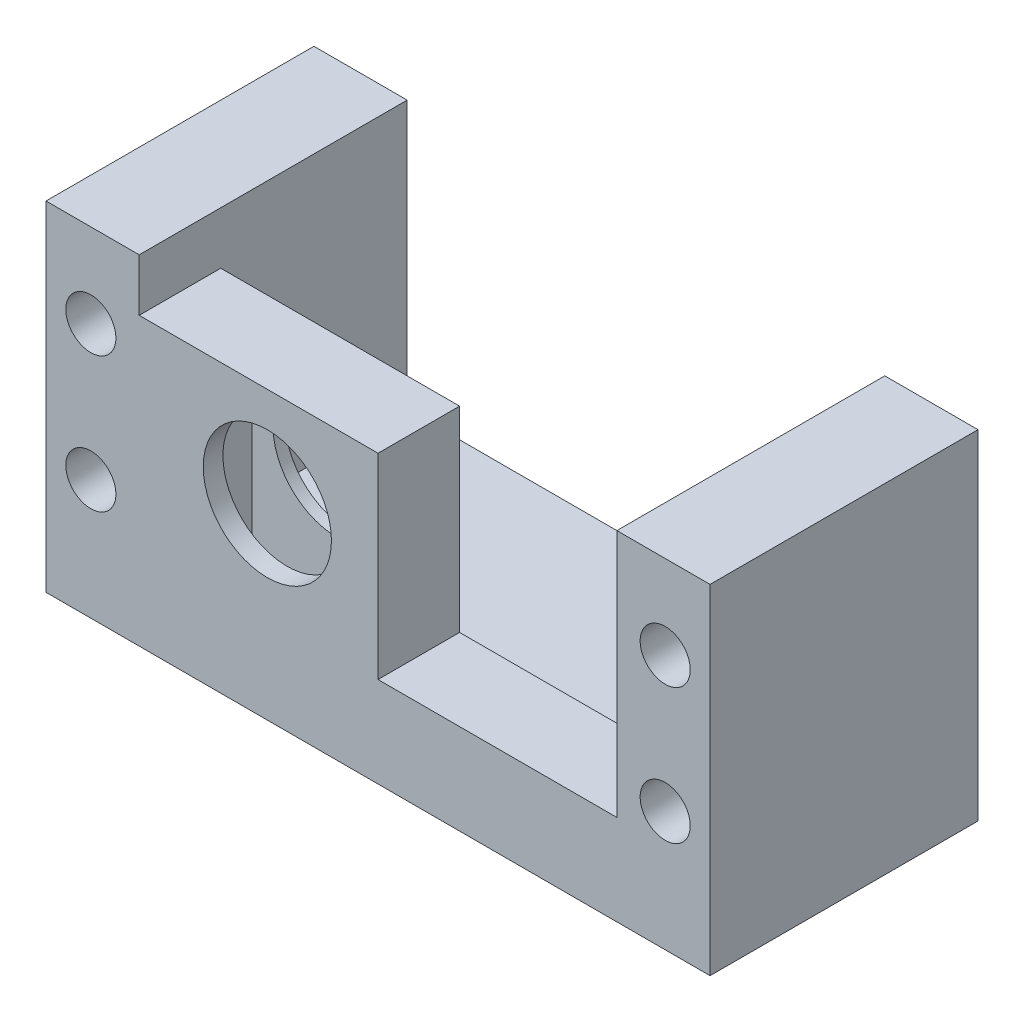
SolidWorks part; units mm, degrees
ref_plane "Спереди" through (0, 0, 0) normal (0, 0, 1) x (1, 0, 0)
ref_plane "Сверху" through (0, 0, 0) normal (0, 1, 0) x (1, 0, 0)
ref_plane "Справа" through (0, 0, 0) normal (1, 0, 0) x (0, 0, -1)
sketch "Эскиз1" plane through (0, 0, 0) normal (0, 0, 1) x (1, 0, 0)
  line L2 (-59.1906, -40.1769) -> (-59.1906, -15.0857)
  line L3 (-59.1906, -15.0857) -> (-51.1906, -15.0857)
  line L4 (-2.1906, -38.0857) -> (-2.1906, -15.0857)
  line L8 (-2.1906, -15.0857) -> (-10.1906, -15.0857)
  line L9 (-10.1906, -15.0857) -> (-10.1906, -38.0857)
  line L10 (-51.1906, -15.0857) -> (-51.1906, -38.0857)
  line L11 (-51.1906, -38.0857) -> (-10.1906, -38.0857)
  line L12 (-59.1906, -40.1769) -> (-59.1906, -44.1769)
  line L13 (-59.1906, -44.1769) -> (-2.1906, -44.1769)
  line L14 (-2.1906, -44.1769) -> (-2.1906, -38.0857)
  point P0 (0, 0)
extrude "Бобышка-Вытянуть1" add sketch "Эскиз1" along normal blind 23
sketch "Эскиз3" plane through (-59.1906, 0, 0) normal (-1, 0, 0) x (0, 0, 1)
  line L5 (0, -15.0857) -> (0, -44.1769) construction
  line L6 (15, -15.0857) -> (0, -15.0857) construction
  line L7 (15, -15.0857) -> (15, -38.2478) construction
  line L8 (15, -38.2478) -> (0, -38.2478) construction
  line L9 (0, -15.0857) -> (0, -38.2478) construction
sketch "Эскиз5" plane through (0, 0, 23) normal (0, 0, 1) x (1, 0, 0)
  line L0 (-51.1906, -38.0857) -> (-51.1906, -15.0857) construction
  line L1 (-10.1906, -28.0857) -> (-24.1906, -28.0857) construction
  line L6 (-30.6906, -18.0857) -> (-30.6906, -34.9839) construction
  line L11 (-51.1906, -28.0857) -> (-37.1906, -28.0857) construction
  line L12 (-10.1906, -38.0857) -> (-51.1906, -38.0857) construction
  line L13 (-10.1906, -38.0857) -> (-10.1906, -18.0857) construction
  line L14 (-10.1906, -18.0857) -> (-51.1906, -18.0857) construction
  line L15 (-51.1906, -38.0857) -> (-51.1906, -18.0857) construction
  line L16 (-21.1906, -34.9839) -> (-51.1906, -34.9839) construction
  line L18 (-21.1906, -19.5857) -> (-51.1906, -19.5857)
  line L19 (-51.1906, -34.9839) -> (-51.1906, -19.5857)
  line L20 (-21.1906, -19.5857) -> (-10.1906, -19.5857)
  line L22 (-21.1906, -34.9839) -> (-10.1906, -34.9839) construction
  line L23 (-10.1906, -19.5857) -> (-10.1906, -34.9839)
  line L24 (-10.1906, -38.0857) -> (-51.1906, -38.0857)
  line L25 (-51.1906, -38.0857) -> (-51.1906, -34.9839)
  line L26 (-10.1906, -38.0857) -> (-10.1906, -34.9839)
  circle A5 centre (-21.1906, -28.0857) radius 2.7
  circle A6 centre (-40.1906, -28.0857) radius 5.5
extrude "Бобышка-Вытянуть6" add sketch "Эскиз5" against normal blind 7
sketch "Эскиз6" plane through (0, 0, 23) normal (0, 0, 1) x (1, 0, 0)
  line L0 (-51.1906, -19.5857) -> (-51.1906, -15.0857) construction
  line L3 (-10.1906, -18.0857) -> (-51.1906, -18.0857)
  line L4 (-51.1906, -38.0857) -> (-51.1906, -18.0857)
  line L5 (-2.1906, -38.0857) -> (-59.1906, -38.0857) construction
  line L6 (-2.1906, -44.1769) -> (-2.1906, -15.0857) construction
  line L7 (-6.0406, -38.0857) -> (-6.0406, -29.5857) construction
  line L8 (-59.1906, -15.0857) -> (-59.1906, -44.1769) construction
  line L9 (-10.1906, -18.0857) -> (-2.1906, -18.0857) construction
  line L10 (-6.0406, -18.0857) -> (-6.0406, -26.5857) construction
  line L11 (-6.0406, -22.2857) -> (-10.1906, -22.2857) construction
  line L12 (-30.6906, -38.0857) -> (-30.6906, -18.0857) construction
  line L13 (-10.1906, -18.0857) -> (-10.1906, -38.0857) construction
  line L14 (-6.0406, -33.8857) -> (-10.1906, -33.8857) construction
  circle A1 centre (-6.0406, -33.8857) radius 2.15
  circle A3 centre (-6.0406, -22.2857) radius 2.15
  circle A4 centre (-55.3406, -22.2857) radius 2.15
  circle A5 centre (-55.3406, -33.8857) radius 2.15
extrude "Вырез-Вытянуть2" cut sketch "Эскиз6" against normal through all contours A1 | A3 | A5 | A4 region at (-6.0406, -33.8857, 23) region at (-6.0406, -22.2857, 23) region at (-55.3406, -22.2857, 23) region at (-55.3406, -33.8857, 23)
sketch "Эскиз8" plane through (0, 0, 23) normal (0, 0, 1) x (1, 0, 0)
  line L1 (-10.1906, -19.5857) -> (-30.6906, -19.5857)
  line L2 (-10.1906, -19.5857) -> (-10.1906, -36.4088)
  line L3 (-10.1906, -36.4088) -> (-30.6906, -36.4088)
  line L4 (-30.6906, -19.5857) -> (-30.6906, -36.4088)
extrude "Вырез-Вытянуть4" cut sketch "Эскиз8" against normal up to surface (7 mm away) up to face at (-45.6906, -28.0857, 16)
sketch "Эскиз16" plane through (0, 0, 23) normal (0, 0, 1) x (1, 0, 0)
  line L0 (-40.1906, -21.4357) -> (-40.1906, -34.7357)
  line L1 (-40.1906, -21.4357) -> (-43.9534, -21.4357) construction
  line L2 (-43.9534, -21.4357) -> (-43.9534, -44.1769) construction
  line L3 (-59.1906, -44.1769) -> (-2.1906, -44.1769) construction
  line L4 (-40.1906, -28.0857) -> (-40.1906, -44.1769) construction
  line L5 (-40.1906, -44.1769) -> (-39.0508, -41.093) construction
  point P4 (-40.1906, -28.0857)
sketch "Эскиз14" plane through (0, -44.1769, 0) normal (0, -1, 0) x (-1, 0, 0)
  line L0 (40.2278, -23) -> (40.2278, -19.1629) construction
  line L1 (59.1906, -23) -> (2.1906, -23) construction
  line L3 (32.9778, -21.3129) -> (47.4778, -21.3129)
  line L4 (32.9778, -21.3129) -> (32.9778, -17.0129)
  line L5 (32.9778, -17.0129) -> (47.4778, -17.0129)
  line L6 (47.4778, -21.3129) -> (47.4778, -17.0129)
  line L7 (32.9778, -21.3129) -> (47.4778, -17.0129) construction
  line L8 (32.9778, -17.0129) -> (47.4778, -21.3129) construction
  point P8 (0, 0)
extrude "Вырез-Вытянуть7" cut sketch "Эскиз14" against normal blind 22.74
